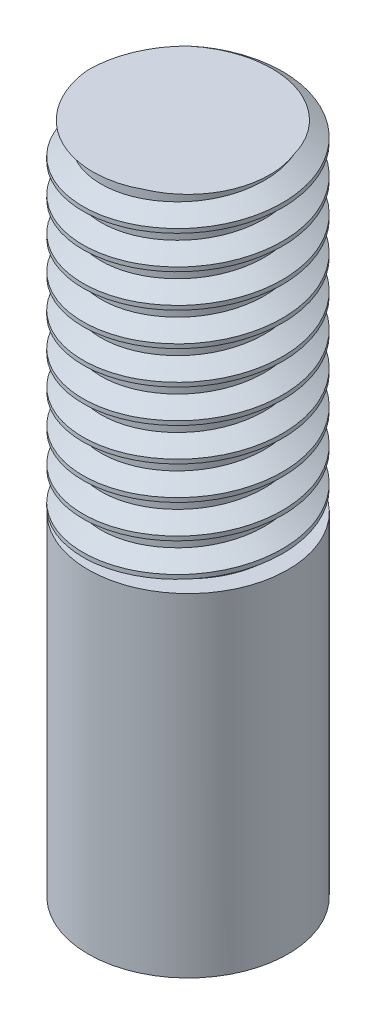
SolidWorks part; units mm, degrees
ref_plane "Front Plane" through (0, 0, 0) normal (0, 0, 1) x (1, 0, 0)
ref_plane "Top Plane" through (0, 0, 0) normal (0, 1, 0) x (1, 0, 0)
ref_plane "Right Plane" through (0, 0, 0) normal (1, 0, 0) x (0, 0, -1)
sketch "Sketch1" plane through (0, 0, 0) normal (0, 1, 0) x (1, 0, 0)
  circle A0 centre (-0.0039, 0) radius 3
extrude "Boss-Extrude1" add sketch "Sketch1" along normal blind 10 contours A0
thread "Thread1" pitch 1 method cut trim with start face yes trim with end face yes profile "Thread Profile2" start angle 0, offset 1, length 12, pitch 1, diameter 6
ref_plane "Plane2" through (-3.0039, 11, 0) normal (0, 0, 1) x (-1, 0, 0)
sketch "Thread Profile2" plane through (-3.0039, 11, 0) normal (0, 0, 1) x (-1, 0, 0)
  line L0 (0, 0) -> (0, 1) construction
  line L11 (0, 0) -> (0, 0.875)
  line L12 (0, 0.875) -> (-0.5413, 0.5625)
  line L13 (-0.5413, 0.5625) -> (-0.5413, 0.3125)
  line L15 (-0.5413, 0.3125) -> (0, 0)
  line L17 (-0.5413, 0.4375) -> (0, 0.4375) construction
  point P2 (0, 0)
  dimension "Pitch" = 1
  dimension "Profile_Angle" = 60
  dimension "Profile_Land" = 0.25
  dimension "Profile_Height" = 0.5413
sketch "Sketch13" plane through (0, 0, 0) normal (0, 1, 0) x (1, 0, 0)
  circle A0 centre (0, 0) radius 3
extrude "Boss-Extrude2" add sketch "Sketch13" against normal blind 10
